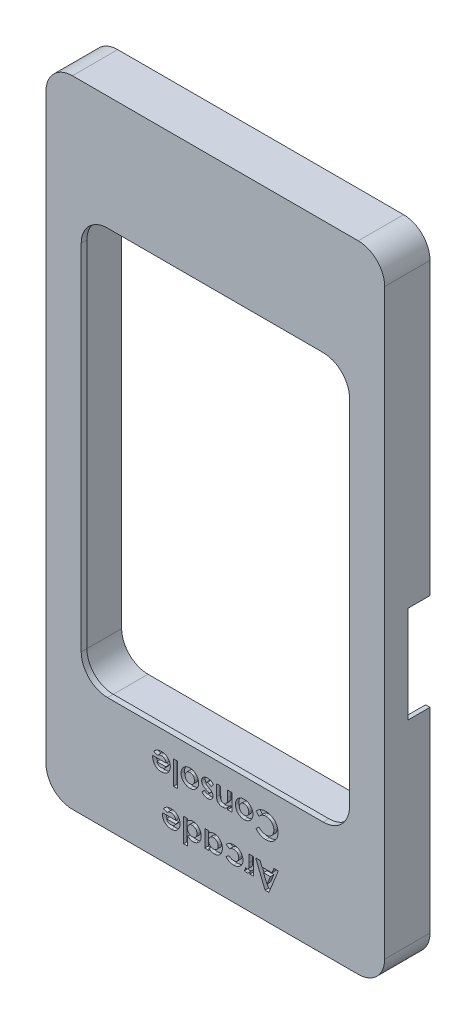
SolidWorks part; units mm, degrees
ref_plane "Ebene vorne" through (0, 0, 0) normal (1, 0, 0) x (0, 1, 0)
ref_plane "Ebene oben" through (0, 0, 0) normal (0, 0, 1) x (0, 1, 0)
ref_plane "Ebene rechts" through (0, 0, 0) normal (0, 1, 0) x (-1, 0, 0)
sketch "DiplayCase" plane through (0, 0, 0) normal (0, 0, 1) x (0, 1, 0)
  line L1 (-46.22, -30.5) -> (46.22, -30.5)
  line L2 (-46.22, -30.5) -> (-46.22, 30.5)
  line L3 (-46.22, 30.5) -> (46.22, 30.5)
  line L4 (46.22, -30.5) -> (46.22, 30.5)
  line L5 (-46.22, -30.5) -> (46.22, 30.5) construction
  line L6 (-46.22, 30.5) -> (46.22, -30.5) construction
  line L7 (-72.22, -38.5) -> (72.22, -38.5)
  line L8 (-72.22, -38.5) -> (-72.22, 38.5)
  line L9 (-72.22, 38.5) -> (72.22, 38.5)
  line L10 (72.22, -38.5) -> (72.22, 38.5)
  line L11 (-72.22, -38.5) -> (72.22, 38.5) construction
  line L12 (-72.22, 38.5) -> (72.22, -38.5) construction
  point P0 (0, 0)
  point P6 (0, 0)
  dimension "D1" = 61
  dimension "D2" = 92.44
  dimension "D3" = 8
  dimension "D4" = 26
extrude "UpperCase" add sketch "DiplayCase" along normal blind 10.3
fillet "Verrundung1" radius 6 4 edges at (30.5, 46.22, 5.15) (-30.5, 46.22, 5.15) (30.5, -46.22, 5.15) (-30.5, -46.22, 5.15)
sketch "Skizze2" plane through (0, 0, 0) normal (0, 0, -1) x (1, 0, 0)
  line L1 (-31.6, -47.32) -> (31.6, -47.32)
  line L2 (-31.6, -47.32) -> (-31.6, 47.32)
  line L3 (-31.6, 47.32) -> (31.6, 47.32)
  line L4 (31.6, -47.32) -> (31.6, 47.32)
  line L5 (-31.6, -47.32) -> (31.6, 47.32) construction
  line L6 (-31.6, 47.32) -> (31.6, -47.32) construction
  point P0 (0, 0)
  dimension "D1" = 63.2
  dimension "D2" = 94.64
extrude "Schnitt-Linear austragen1" cut sketch "Skizze2" against normal blind 9
fillet "Verrundung2" radius 6 4 edges at (38.5, -72.22, 5.15) (-38.5, -72.22, 5.15) (38.5, 72.22, 5.15) (-38.5, 72.22, 5.15)
fillet "Verrundung3" radius 6 4 edges at (-31.6, 47.32, 4.5) (31.6, 47.32, 4.5) (31.6, -47.32, 4.5) (-31.6, -47.32, 4.5)
shell "Wandung2" thickness 1 removed face at (0, 0, 0)
sketch "Skizze8" plane through (0, 0, 10.3) normal (0, 0, 1) x (0, -1, 0)
  line L0 (46.22, 0) -> (72.22, 0) construction
  line L1 (46.22, -24.5) -> (46.22, 24.5) construction
  line L2 (72.22, -32.5) -> (72.22, 32.5) construction
  line L3 (60.9348, 18.5) -> (60.9348, -18.5) construction
  text T0 "Arcade \r\nConsole" font "Century Gothic" height in points 20
  point P9 (0, 0)
  point P10 (60.9348, 0)
extrude "Text_ArcadeConsole" cut sketch "Skizze8" against normal blind 0.8
sketch "Skizze11" plane through (0, 47.32, 0) normal (0, -1, 0) x (1, 0, 0)
  line L1 (-10.85, -4.17) -> (10.85, -4.17)
  line L2 (-10.85, -4.17) -> (-10.85, 4.17)
  line L3 (-10.85, 4.17) -> (10.85, 4.17)
  line L4 (10.85, -4.17) -> (10.85, 4.17)
  line L5 (-10.85, -4.17) -> (10.85, 4.17) construction
  line L6 (-10.85, 4.17) -> (10.85, -4.17) construction
  point P0 (0, 0)
  dimension "D1" = 21.7
  dimension "D2" = 8.34
extrude "Hole_DisplayCables" cut sketch "Skizze11" against normal blind 1
sketch "Skizze12" plane through (0, 0, 9.3) normal (0, 0, -1) x (1, 0, 0)
  line L1 (-31.5, -66) -> (31.5, -66) construction
  line L2 (-31.5, -66) -> (-31.5, 66) construction
  line L3 (-31.5, 66) -> (31.5, 66) construction
  line L4 (31.5, -66) -> (31.5, 66) construction
  line L5 (-31.5, -66) -> (31.5, 66) construction
  line L6 (-31.5, 66) -> (31.5, -66) construction
  circle A2 centre (34, 68) radius 2.5
  circle A3 centre (34, 68) radius 1.25
  circle A4 centre (-34, 68) radius 2.5
  circle A5 centre (-34, 68) radius 1.25
  circle A6 centre (34, -68) radius 2.5
  circle A7 centre (34, -68) radius 1.25
  circle A8 centre (-34, -68) radius 2.5
  circle A9 centre (-34, -68) radius 1.25
  point P0 (0, 0)
  dimension "D3" = 5
  dimension "D4" = 2.5
  dimension "D6" = 2.5
  dimension "D7" = 5
  dimension "D8" = 2.5
  dimension "D11" = 5
  dimension "D12" = 2.5
  dimension "D15" = 5
  dimension "D16" = 2.5
  dimension "D1" = 63
  dimension "D2" = 132
  dimension "D5" = 2
  dimension "D9" = 2.5
  dimension "D10" = 2
  dimension "D13" = 2.5
  dimension "D14" = 2
extrude "Aufsatz-Linear austragen4" add sketch "Skizze12" along normal blind 4 contours A6 | A7 | A4 | A5 | A3 | A2 | A8 | A9
sketch "Skizze16" plane through (38.5, 0, 0) normal (1, 0, 0) x (0, 1, 0)
  line L0 (-66.22, 0) -> (66.22, 0) construction
  line L2 (0.22, 0) -> (-21.78, 0)
  line L3 (0.22, 0) -> (0.22, 5)
  line L4 (0.22, 5) -> (-21.78, 5)
  line L5 (-21.78, 0) -> (-21.78, 5)
  dimension "D1" = 66
  dimension "D2" = 22
  dimension "D3" = 5
extrude "Schnitt-Linear austragen3" cut sketch "Skizze16" against normal blind 11
